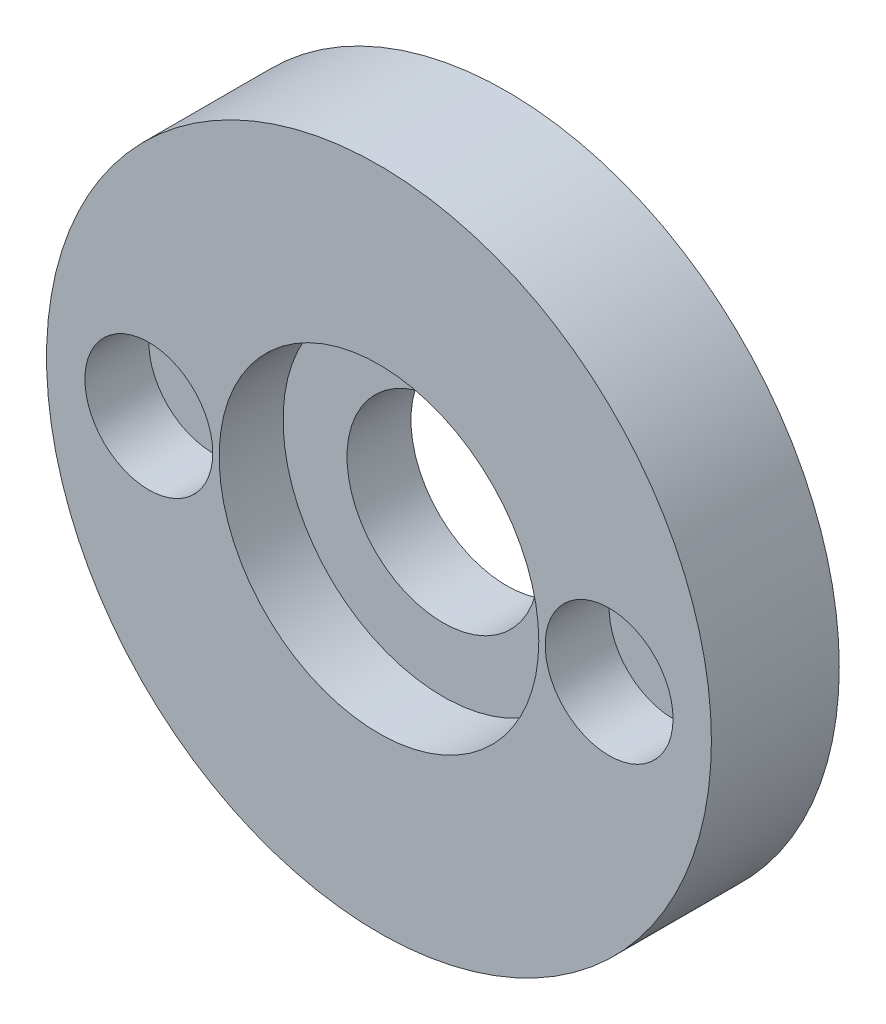
SolidWorks part; units mm, degrees
ref_plane "前视基准面" through (0, 0, 0) normal (0, 0, 1) x (1, 0, 0)
ref_plane "上视基准面" through (0, 0, 0) normal (0, 1, 0) x (1, 0, 0)
ref_plane "右视基准面" through (0, 0, 0) normal (1, 0, 0) x (0, 0, -1)
sketch "草图4" plane through (0, 0, 0) normal (0, 0, 1) x (1, 0, 0)
  line L0 (-26, 0) -> (-18, 0) construction
  line L1 (0, 0) -> (0, 19.3074) construction
  circle A0 centre (0, 0) radius 26
  circle A1 centre (0, 0) radius 7.5
  circle A2 centre (-18, 0) radius 2
  circle A4 centre (-18, 0) radius 5
  circle A6 centre (18, 0) radius 5
  circle A7 centre (18, 0) radius 2
  dimension "D1" = 52
  dimension "D2" = 10
extrude "凸台-拉伸2" add sketch "草图4" along normal blind 10 contours A0 A1 A4 A6 region at (-25.2646, 0, 0)
extrude "凸台-拉伸3" add sketch "草图4<4>" along normal blind 5 contours A4 A2 | A6 A7 region at (-22.8586, 0, 0) region at (13.1414, 0, 0)
sketch "草图4<4>" plane through (0, 0, 0) normal (0, 0, 1) x (1, 0, 0) same geometry as "草图4"
sketch "草图5" plane through (0, 0, 10) normal (0, 0, 1) x (1, 0, 0)
  circle A0 centre (0, 0) radius 12.5
  dimension "D1" = 25
extrude "切除-拉伸3" cut sketch "草图5" against normal blind 5
